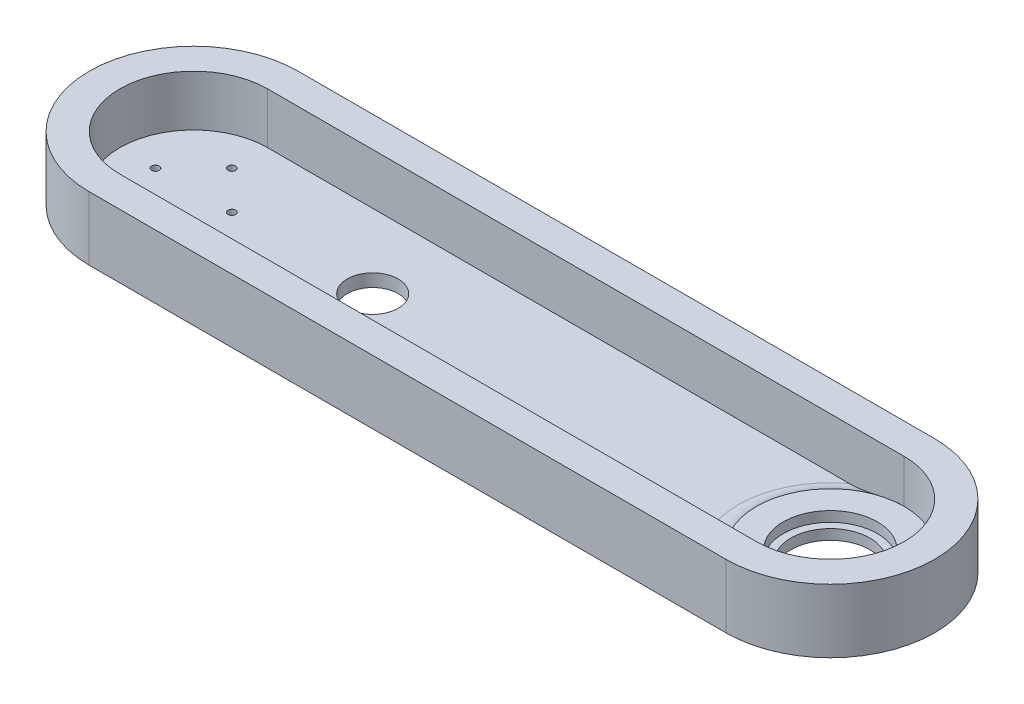
SolidWorks part; units mm, degrees
ref_plane "Front Plane" through (0, 0, 0) normal (0, 0, 1) x (1, 0, 0)
ref_plane "Top Plane" through (0, 0, 0) normal (0, 1, 0) x (1, 0, 0)
ref_plane "Right Plane" through (0, 0, 0) normal (1, 0, 0) x (0, 0, -1)
sketch "Sketch1" plane through (0, 0, 0) normal (0, 1, 0) x (1, 0, 0)
  line L0 (0, 0) -> (250, 0) construction
  line L1 (0, 29) -> (250, 29)
  line L2 (0, -41) -> (250, -41)
  line L3 (0, -29) -> (250, -29)
  line L4 (0, 41) -> (250, 41)
  arc A0 (0, 29) -> (0, -29) centre (0, 0) ccw
  arc A1 (250, -29) -> (250, 29) centre (250, 0) ccw
  arc A2 (0, 41) -> (0, -41) centre (0, 0) ccw
  arc A3 (250, -41) -> (250, 41) centre (250, 0) ccw
  dimension "D1" = 58
  dimension "D3" = 12
  dimension "D2" = 250
extrude "Boss-Extrude1" add sketch "Sketch1" along normal blind 20
extrude "Boss-Extrude2" add sketch "Sketch1<2>" against normal blind 5 contours L3 A1 L1 A0 | L2 A3 L4 A2 A1 L3 A0 L1 region at (125, 0, 0) region at (-37.5802, 0, 0)
sketch "Sketch1<2>" plane through (0, 0, 0) normal (0, 1, 0) x (1, 0, 0) same geometry as "Sketch1"
sketch "Sketch3" plane through (0, 0, 0) normal (0, 1, 0) x (1, 0, 0)
  circle A0 centre (0, 0) radius 15 construction
  circle A1 centre (0, 15) radius 1.5
  circle A2 centre (15, 0) radius 1.5
  circle A3 centre (0, -15) radius 1.5
  circle A4 centre (-15, 0) radius 1.5
  point P14 (0, 0)
  dimension "D1" = 30
  dimension "D2" = 3
  dimension "D3" = 4
extrude "Cut-Extrude1" cut sketch "Sketch3" against normal through all both and the other way through all
sketch "Sketch4" plane through (0, 0, 0) normal (0, 1, 0) x (1, 0, 0)
  circle A0 centre (250, 0) radius 29
extrude "Boss-Extrude3" add sketch "Sketch4" along normal blind 3
sketch "Sketch5" plane through (0, 3, 0) normal (0, 1, 0) x (1, 0, 0)
  circle A0 centre (250, 0) radius 18.5
  dimension "D1" = 37
extrude "Cut-Extrude2" cut sketch "Sketch5" against normal blind 4 contours A0
sketch "Sketch6" plane through (0, -1, 0) normal (0, 1, 0) x (1, 0, 0)
  circle A0 centre (250, 0) radius 15.5
  dimension "D1" = 31
extrude "Cut-Extrude3" cut sketch "Sketch6" against normal through all both and the other way through all
fillet "Fillet1" radius 10 1 edges at (221, 0, 0)
sketch "Sketch7" plane through (0, 0, 0) normal (0, 1, 0) x (1, 0, 0)
  line L0 (0, 0) -> (250, 0) construction
  circle A0 centre (70.3, 0) radius 10
  dimension "D1" = 20
  dimension "D2" = 70.3
extrude "Cut-Extrude4" cut sketch "Sketch7" against normal through all both and the other way through all
